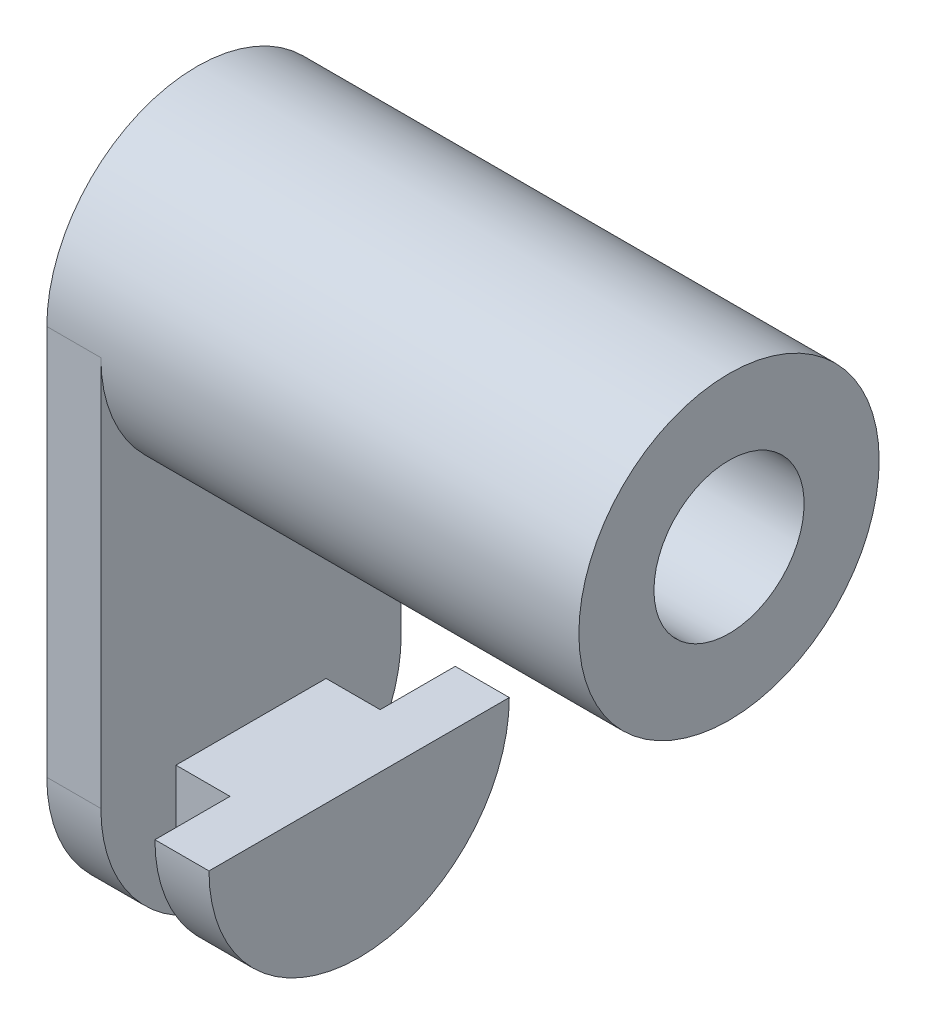
SolidWorks part; units mm, degrees
ref_plane "Front Plane" through (0, 0, 0) normal (1, 0, 0) x (0, 1, 0)
ref_plane "Top Plane" through (0, 0, 0) normal (0, 0, 1) x (0, 1, 0)
ref_plane "Right Plane" through (0, 0, 0) normal (0, 1, 0) x (-1, 0, 0)
sketch "Sketch1" plane through (0, 0, 0) normal (1, 0, 0) x (0, 1, 0)
  circle A0 centre (0, 0) radius 3.175
  circle A1 centre (0, 0) radius 3
  circle A2 centre (0, 0) radius 6.35
  dimension "D1" = 6
  dimension "D2" = 6.35
  dimension "D3" = 12.7
extrude "Boss-Extrude1" add sketch "Sketch1" along normal blind 22.5 contours A2 A0 region at (0, -6.1704, 0)
extrude "Boss-Extrude2" add sketch "Sketch1<3>" along normal blind 7 contours A0 A1 region at (0, -3.0852, 0)
sketch "Sketch1<3>" plane through (0, 0, 0) normal (1, 0, 0) x (0, 1, 0) same geometry as "Sketch1"
sketch "Sketch3" plane through (0, 0, 0) normal (0, 0, 1) x (0, 1, 0)
  line L0 (0, 0) -> (-22.86, 0)
  line L1 (-22.86, 0) -> (-22.86, -2.286)
  line L2 (-22.86, -2.286) -> (0, -2.286)
  line L4 (0, 0) -> (0, -22.5)
  line L5 (-22.86, -2.286) -> (-22.86, -4.572)
  line L6 (-22.86, -4.572) -> (0, -4.572)
  line L7 (-6.35, -22.5) -> (6.35, -22.5) construction
  line L8 (-16.51, -2.286) -> (-16.51, -4.572)
  line L9 (-16.51, -4.572) -> (-16.51, -6.858)
  line L10 (-16.51, -6.858) -> (-22.86, -6.858)
  line L11 (-22.86, -6.858) -> (-22.86, -4.572)
  dimension "D1" = 22.86
  dimension "D2" = 2.286
  dimension "D3" = 2.286
  dimension "D4" = 6.35
  dimension "D5" = 2.286
extrude "Boss-Extrude3" add sketch "Sketch3" along normal blind 6.35 and the other way blind 6.35 contours L4 L0 L1 L2 | L11 L10 L9 L6 region at (1.143, -11.43, 0) region at (5.715, -19.685, 0)
extrude "Boss-Extrude4" add sketch "Sketch3<4>" along normal blind 3.175 and the other way blind 3.175 contours L8 L2 L5 L6 region at (3.429, -19.685, 0)
sketch "Sketch3<4>" plane through (0, 0, 0) normal (0, 0, 1) x (0, 1, 0) same geometry as "Sketch3"
extrude "Cut-Extrude2" cut sketch "Sketch1<4>" along normal through all contours A1 region at (0, 0, 0)
sketch "Sketch1<4>" plane through (0, 0, 0) normal (1, 0, 0) x (0, 1, 0) same geometry as "Sketch1"
fillet "Fillet1" radius 6.35 2 edges at (1.143, -22.86, -6.35) (1.143, -22.86, 6.35)
